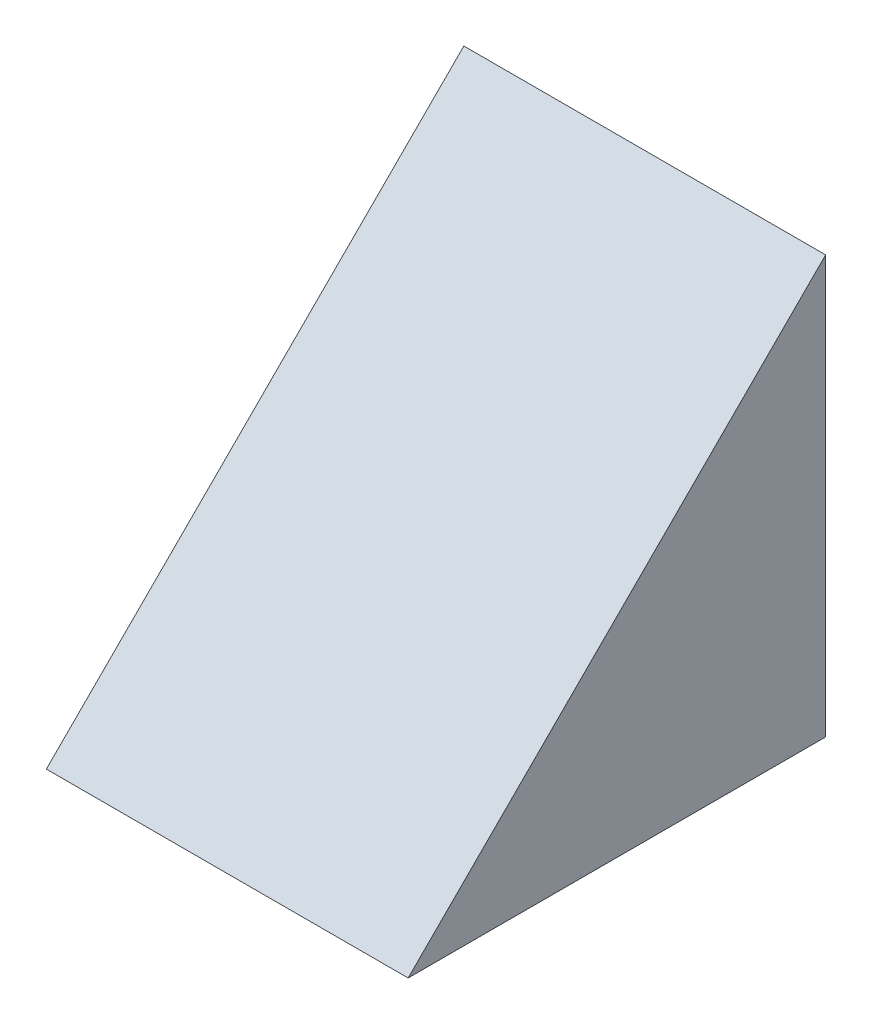
SolidWorks part; units mm, degrees
ref_plane "Front Plane" through (0, 0, 0) normal (0, 0, 1) x (1, 0, 0)
ref_plane "Top Plane" through (0, 0, 0) normal (0, 1, 0) x (1, 0, 0)
ref_plane "Right Plane" through (0, 0, 0) normal (1, 0, 0) x (0, 0, -1)
sketch "Sketch1" plane through (-5.958, 0, 0) normal (1, 0, 0) x (0, 0, -1)
  line L0 (-7.303, -51.9052) -> (-7.303, -21.9052)
  line L1 (-7.303, 48.0948) -> (-7.303, -51.9052) construction
  line L2 (-7.303, -21.9052) -> (-37.303, -51.9052)
  line L3 (-100.953, -51.9052) -> (-0.953, -51.9052) construction
  line L4 (-37.303, -51.9052) -> (-7.303, -51.9052)
  dimension "D1" = 30
  dimension "D2" = 30
sketch "Sketch2" plane through (-5.958, 0, 0) normal (1, 0, 0) x (0, 0, -1)
  line L0 (-7.303, -51.9052) -> (-7.303, -21.9052)
  line L1 (-7.303, 48.0948) -> (-7.303, -51.9052) construction
  line L2 (-7.303, -21.9052) -> (-37.303, -51.9052)
  line L3 (-100.953, -51.9052) -> (-0.953, -51.9052) construction
  line L4 (-37.303, -51.9052) -> (-7.303, -51.9052)
  dimension "D1" = 30
  dimension "D2" = 30
extrude "Boss-Extrude2" add sketch "Sketch2" against normal blind 26
